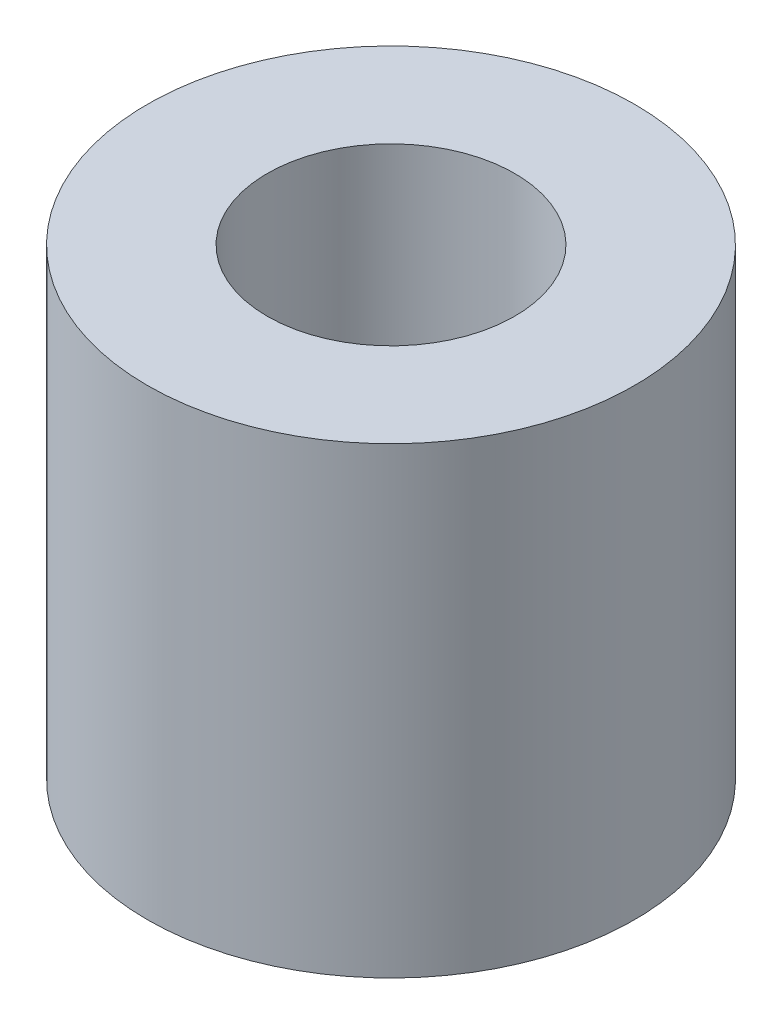
SolidWorks part; units mm, degrees
ref_plane "Front Plane" through (0, 0, 0) normal (0, 0, 1) x (1, 0, 0)
ref_plane "Top Plane" through (0, 0, 0) normal (0, 1, 0) x (1, 0, 0)
ref_plane "Right Plane" through (0, 0, 0) normal (1, 0, 0) x (0, 0, -1)
sketch "Sketch1" plane through (0, 0, 0) normal (0, 1, 0) x (1, 0, 0)
  circle A0 centre (0, 0) radius 6.35
  arc A4 (5.6286, -2.9396) -> (-4.0286, 4.9085) centre (0, 0) ccw construction
  circle A5 centre (0, 0) radius 3.2258
  circle A6 centre (0, 0) radius 3.2258
  dimension "D1" = 0.0508
extrude "Boss-Extrude1" add sketch "Sketch1" along normal up to surface (12.0623 mm away)
